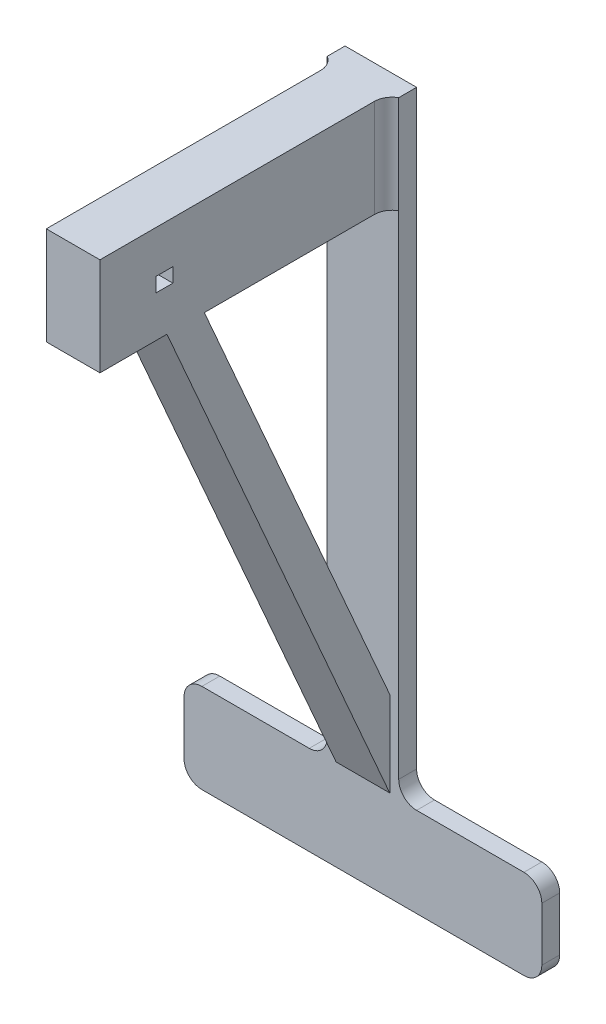
SolidWorks part; units mm, degrees
ref_plane "前视基准面" through (0, 0, 0) normal (0, 0, 1) x (1, 0, 0)
ref_plane "上视基准面" through (0, 0, 0) normal (0, 1, 0) x (1, 0, 0)
ref_plane "右视基准面" through (0, 0, 0) normal (1, 0, 0) x (0, 0, -1)
sketch "草图1" plane through (0, 0, 0) normal (0, 0, 1) x (1, 0, 0)
  line L1 (50, 12.5) -> (-50, 12.5)
  line L2 (50, 12.5) -> (50, -12.5)
  line L3 (50, -12.5) -> (-50, -12.5)
  line L4 (-50, 12.5) -> (-50, -12.5)
  line L5 (0, -12.5) -> (0, 12.5) construction
  line L6 (50, 0) -> (-50, 0) construction
  point P0 (0, 0)
  dimension "D1" = 25
  dimension "D2" = 100
extrude "凸台-拉伸1" add sketch "草图1" along normal blind 5
sketch "草图2" plane through (0, 12.5, 0) normal (0, 1, 0) x (1, 0, 0)
  line L6 (50, 0) -> (-50, 0) construction
  line L7 (10, -5) -> (-10, -5)
  line L8 (10, -5) -> (10, 0)
  line L9 (10, 0) -> (-10, 0)
  line L10 (-10, -5) -> (-10, 0)
  line L11 (0, 0) -> (0, -5) construction
  line L12 (10, -2.5) -> (-10, -2.5) construction
  point P0 (0, -2.5)
  point P4 (0, 0)
  point P5 (0, -5.0752)
  dimension "D1" = 20
  dimension "D2" = 5
extrude "凸台-拉伸2" add sketch "草图2" along normal blind 170
sketch "草图3" plane through (0, 0, 5) normal (0, 0, 1) x (1, 0, 0)
  line L0 (-10, 182.5) -> (10, 182.5) construction
  line L1 (7.5, 155.1273) -> (-7.5, 155.1273)
  line L2 (7.5, 155.1273) -> (7.5, 182.5)
  line L3 (7.5, 182.5) -> (-7.5, 182.5)
  line L4 (-7.5, 155.1273) -> (-7.5, 182.5)
  line L5 (0, 182.5) -> (0, 155.1273) construction
  line L6 (7.5, 168.8136) -> (-7.5, 168.8136) construction
  point P0 (0, 168.8136)
  point P6 (0, 14.91)
  point P7 (-0.2282, 15.042)
  point P8 (-0.4559, 168.8136)
  point P9 (0, 0)
  point P10 (0, 182.5)
  dimension "D1" = 15
extrude "凸台-拉伸3" add sketch "草图3" along normal blind 81
sketch "草图5" plane through (7.5, 0, 0) normal (1, 0, 0) x (0, 0, -1)
  line L3 (-70.3403, 170.6544) -> (-65.613, 170.6544)
  line L4 (-70.3403, 170.6544) -> (-70.3403, 166.6544)
  line L5 (-70.3403, 166.6544) -> (-65.613, 166.6544)
  line L6 (-65.613, 170.6544) -> (-65.613, 166.6544)
  line L7 (-67.9766, 166.6544) -> (-67.9766, 170.6544) construction
  line L8 (-70.3403, 168.6544) -> (-65.613, 168.6544) construction
  point P0 (-67.9766, 168.6544)
  point P2 (-63.4861, 168.6544)
  dimension "D1" = 4
fillet "圆角1" radius 5 2 edges at (-7.5, 168.8136, 5) (7.5, 168.8136, 5)
sketch "草图6" plane through (0, 0, 5) normal (0, 0, 1) x (1, 0, 0)
  line L1 (-7.5, 36.801) -> (7.5, 36.801)
  line L2 (-7.5, 36.801) -> (-7.5, 12.9495)
  line L3 (-7.5, 12.9495) -> (7.5, 12.9495)
  line L4 (7.5, 36.801) -> (7.5, 12.9495)
  line L5 (0, 12.9495) -> (0, 36.801) construction
  line L6 (-7.5, 24.8752) -> (7.5, 24.8752) construction
  point P0 (0, 24.8752)
  point P4 (0, 0)
  point P5 (0, 0)
  point P6 (2.5, 24.4257)
  point P7 (0.3256, 24.8752)
  dimension "D1" = 15
sketch "草图7" plane through (0, 0, 0) normal (1, 0, 0) x (0, 0, -1)
  line L0 (-5, 24.8752) -> (-67.9766, 168.6544)
  point P3 (-53.9592, 168.5729)
  point P5 (-51.8923, 155.042)
sweep "扫描1" add profiles "草图6" path "草图7"
fillet "圆角2" radius 5 2 edges at (-10, 12.5, 2.5) (10, 12.5, 2.5)
fillet "圆角3" radius 5 4 edges at (-50, -12.5, 2.5) (-50, 12.5, 2.5) (50, -12.5, 2.5) (50, 12.5, 2.5)
extrude "切除-拉伸3" cut sketch "草图5" against normal blind 100
